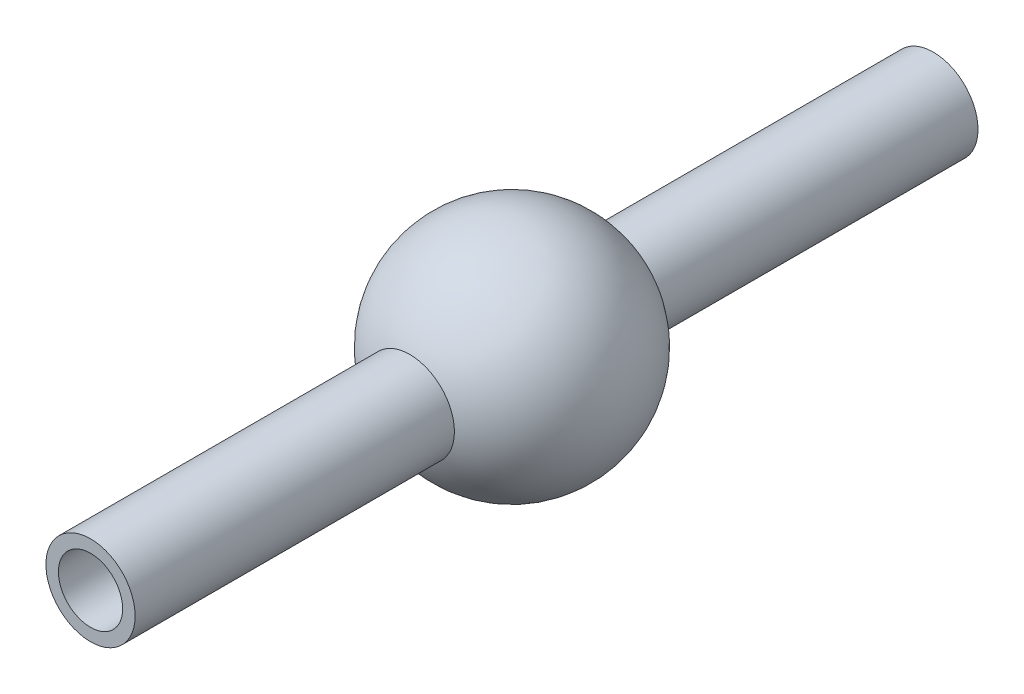
SolidWorks part; units mm, degrees
ref_plane "Front Plane" through (0, 0, 0) normal (0, 0, 1) x (1, 0, 0)
ref_plane "Top Plane" through (0, 0, 0) normal (0, 1, 0) x (1, 0, 0)
ref_plane "Right Plane" through (0, 0, 0) normal (1, 0, 0) x (0, 0, -1)
sketch "Sketch1" plane through (0, 0, 0) normal (0, 1, 0) x (1, 0, 0)
  line L0 (0, 7.935) -> (0, -7.935)
  line L1 (0, 16.8136) -> (0, -16.3242) construction
  arc A0 (0, 7.935) -> (0, -7.935) centre (0, 0) ccw
  dimension "D1" = 15.87
revolve "Revolve1" add sketch "Sketch1" angle 360 about L1
sketch "Sketch2" plane through (0, 0, 0) normal (0, 0, 1) x (1, 0, 0)
  circle A0 centre (0, 0) radius 3.175
  dimension "D1" = 6.35
extrude "Cut-Extrude1" cut sketch "Sketch2" against normal blind 10 and the other way blind 10
sketch "Sketch3" plane through (0, 0, 0) normal (0, 0, 1) x (1, 0, 0)
  circle A0 centre (0, 0) radius 3.175
  circle A1 centre (0, 0) radius 2.286
  dimension "D1" = 4.572
  dimension "D2" = 6.35
extrude "Boss-Extrude1" add sketch "Sketch3" along normal blind 30 and the other way blind 30
